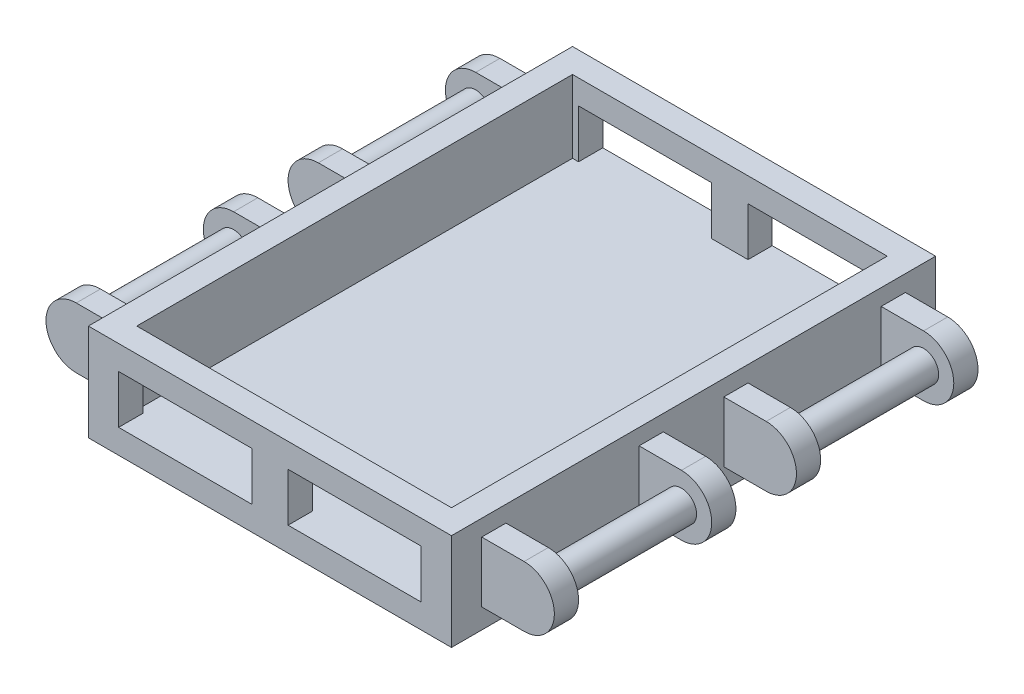
SolidWorks part; units mm, degrees
ref_plane "Front Plane" through (0, 0, 0) normal (0, 0, 1) x (1, 0, 0)
ref_plane "Top Plane" through (0, 0, 0) normal (0, 1, 0) x (1, 0, 0)
ref_plane "Right Plane" through (0, 0, 0) normal (1, 0, 0) x (0, 0, -1)
sketch "Sketch2" plane through (0, 0, 0) normal (0, 1, 0) x (1, 0, 0)
  line L1 (-30, 40) -> (30, 40)
  line L2 (-30, 40) -> (-30, -40)
  line L3 (-30, -40) -> (30, -40)
  line L4 (30, 40) -> (30, -40)
  line L5 (-30, 40) -> (30, -40) construction
  line L6 (-30, -40) -> (30, 40) construction
  point P0 (0, 0)
  dimension "D1" = 80
  dimension "D2" = 60
extrude "Boss-Extrude2" add sketch "Sketch2" along normal blind 16 contours L2 L3 L4 L1
sketch "Sketch6" plane through (0, 16, 0) normal (0, 1, 0) x (1, 0, 0)
  line L1 (-26, 36) -> (26, 36)
  line L2 (-26, 36) -> (-26, -36)
  line L3 (-26, -36) -> (26, -36)
  line L4 (26, 36) -> (26, -36)
  line L5 (-26, 36) -> (26, -36) construction
  line L6 (-26, -36) -> (26, 36) construction
  point P0 (0, 0)
extrude "Cut-Extrude1" cut sketch "Sketch6" against normal blind 12
sketch "Sketch7" plane through (0, 0, -40) normal (0, 0, -1) x (-1, 0, 0)
  line L0 (-30, 16) -> (-30, 0) construction
  line L1 (-3, 12) -> (-25, 12)
  line L2 (-3, 12) -> (-3, 4)
  line L3 (-3, 4) -> (-25, 4)
  line L4 (-25, 12) -> (-25, 4)
  line L5 (-3, 12) -> (-25, 4) construction
  line L6 (-3, 4) -> (-25, 12) construction
  line L7 (25, 12) -> (3, 12)
  line L8 (25, 12) -> (25, 4)
  line L9 (25, 4) -> (3, 4)
  line L10 (3, 12) -> (3, 4)
  line L11 (30, 0) -> (-30, 0) construction
  line L12 (30, 16) -> (30, 0) construction
  point P0 (-14, 8)
  point P5 (-15.945, 6.7876)
  dimension "D1" = 22
  dimension "D2" = 5
  dimension "D3" = 4
  dimension "D4" = 5
  dimension "D5" = 4
  dimension "D6" = 22
  dimension "D7" = 8
  dimension "D8" = 8
extrude "Cut-Extrude2" cut sketch "Sketch7" against normal blind 106 and the other way blind 16
sketch "Sketch8" plane through (30, 0, 0) normal (1, 0, 0) x (0, 0, -1)
  line L1 (-35, 3.3031) -> (-31, 3.3031)
  line L2 (-35, 3.3031) -> (-35, 13.3031)
  line L3 (-35, 13.3031) -> (-31, 13.3031)
  line L4 (-31, 3.3031) -> (-31, 13.3031)
  line L5 (-35, 3.3031) -> (-31, 13.3031) construction
  line L6 (-35, 13.3031) -> (-31, 3.3031) construction
  line L7 (-40, 16) -> (-40, 0) construction
  line L8 (-9, 3.3552) -> (-5, 3.3552)
  line L9 (-9, 3.3552) -> (-9, 13.3552)
  line L10 (-9, 13.3552) -> (-5, 13.3552)
  line L11 (-5, 3.3552) -> (-5, 13.3552)
  line L12 (0, 16) -> (0, 0)
  line L13 (40, 16) -> (-40, 16) construction
  line L14 (35, 13.3031) -> (31, 3.3031) construction
  line L15 (35, 3.3031) -> (31, 13.3031) construction
  line L16 (5, 3.3552) -> (5, 13.3552)
  line L17 (9, 13.3552) -> (5, 13.3552)
  line L18 (9, 3.3552) -> (9, 13.3552)
  line L19 (9, 3.3552) -> (5, 3.3552)
  line L20 (31, 3.3031) -> (31, 13.3031)
  line L21 (35, 13.3031) -> (31, 13.3031)
  line L22 (35, 3.3031) -> (35, 13.3031)
  line L23 (35, 3.3031) -> (31, 3.3031)
  point P0 (-33, 8.3031)
  point P24 (33, 8.3031)
  dimension "D1" = 5
  dimension "D2" = 31
  dimension "D3" = 22
ref_plane "Midsection" through (0, 0, 0) normal (1, 0, 0) x (0, 0, -1)
ref_plane "Midsection (Short)" through (0, 0, 0) normal (0, 0, -1) x (-1, 0, 0)
ref_axis "Strap Mirror" through (30, 16, 0) along (0, -1, 0)
extrude "Boss-Extrude3" add sketch "Sketch8" along normal blind 12 contours L4 L3 L2 L1 | L11 L10 L9 L8 | L18 L17 L16 L19 | L22 L21 L20 L23
fillet "Fillet1" 2 edges at (42, 13.3031, 33) (42, 3.3031, 33) type full round first side face at (36, 13.3031, 33) second side face at (36, 3.3031, 33) middle face at (42, 8.3031, 33)
fillet "Fillet2" 2 edges at (42, 13.3552, 7) (42, 3.3552, 7) type full round first side face at (36, 13.3552, 7) second side face at (36, 3.3552, 7) middle face at (42, 8.3552, 7)
fillet "Fillet3" 2 edges at (42, 13.3552, -7) (42, 3.3552, -7) type full round first side face at (36, 13.3552, -7) second side face at (36, 3.3552, -7) middle face at (42, 8.3552, -7)
fillet "Fillet4" 2 edges at (42, 13.3031, -33) (42, 3.3031, -33) type full round first side face at (36, 13.3031, -33) second side face at (36, 3.3031, -33) middle face at (42, 8.3031, -33)
sketch "Sketch9" plane through (0, 0, 31) normal (0, 0, -1) x (-1, 0, 0)
  circle A0 centre (-37, 8.3031) radius 2.5
  dimension "D1" = 5
extrude "Boss-Extrude4" add sketch "Sketch9" along normal blind 24 and the other way blind 2
mirror "Mirror1" about plane through (0, 0, 0) normal (0, 0, -1) of "Boss-Extrude4"
mirror "Mirror2" about plane through (0, 0, 0) normal (1, 0, 0) of "Boss-Extrude3", "Fillet1", "Fillet2", "Fillet3", "Fillet4", "Boss-Extrude4", "Mirror1"
